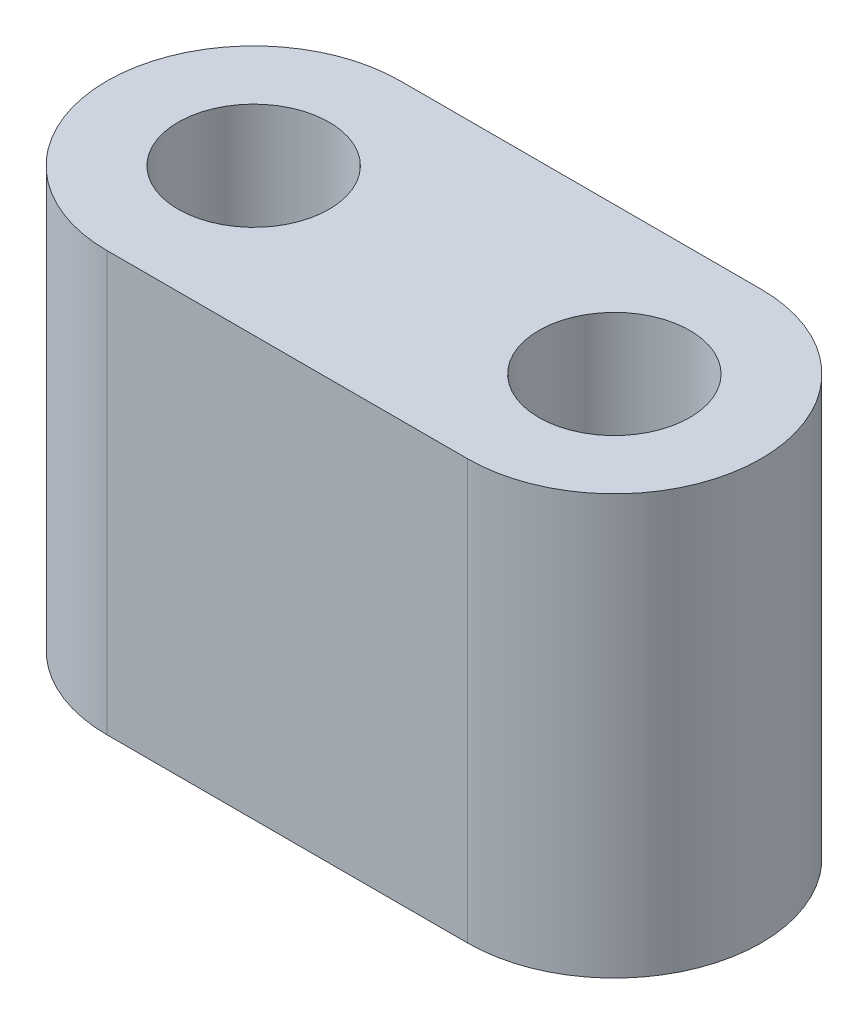
SolidWorks part; units mm, degrees
material "ABS"
ref_plane "Front" through (0, 0, 0) normal (0, 0, 1) x (1, 0, 0)
ref_plane "Top" through (0, 0, 0) normal (0, 1, 0) x (1, 0, 0)
ref_plane "Right" through (0, 0, 0) normal (1, 0, 0) x (0, 0, -1)
ref_axis "X" through (-80.9, 0, 0) along (1, 0, 0)
ref_axis "Y" through (0, -50, 0) along (0, 1, 0)
ref_axis "Z" through (0, 0, -80.9) along (0, 0, 1)
sketch "Sketch1" plane through (0, 0, 0) normal (0, 1, 0) x (1, 0, 0)
  line L0 (-4.3, 0) -> (4.3, 0) construction
  line L1 (-4.3, 3.5) -> (4.3, 3.5)
  line L2 (-4.3, -3.5) -> (4.3, -3.5)
  arc A0 (-4.3, 3.5) -> (-4.3, -3.5) centre (-4.3, 0) ccw
  arc A1 (4.3, -3.5) -> (4.3, 3.5) centre (4.3, 0) ccw
  circle A2 centre (-4.3, 0) radius 1.8
  circle A3 centre (4.3, 0) radius 1.8
  point P3 (0, 0)
  dimension "D2" = 3.6
  dimension "D3" = 5
  dimension "D1" = 7
extrude "Boss-Extrude1" add sketch "Sketch1" along normal mid plane 10
